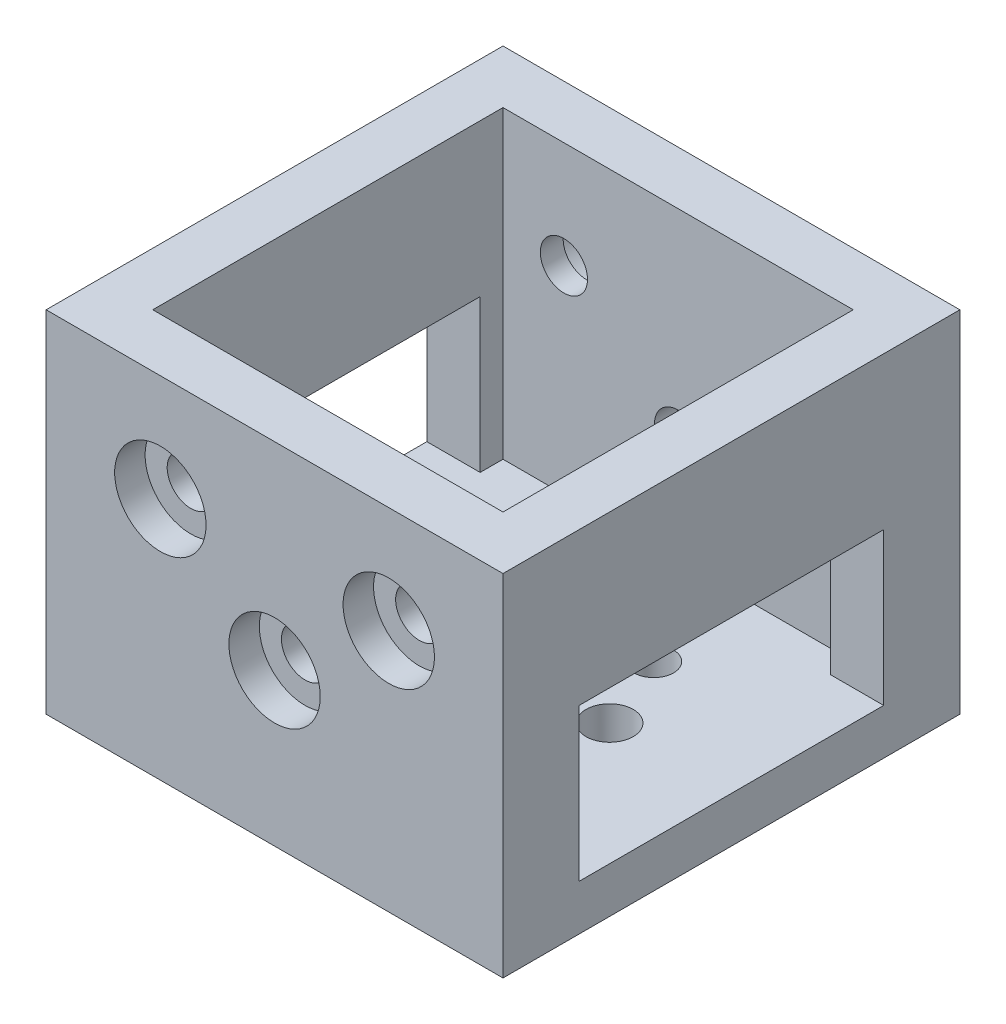
SolidWorks part; units mm, degrees
ref_plane "前视基准面" through (0, 0, 0) normal (0, 0, 1) x (1, 0, 0)
ref_plane "上视基准面" through (0, 0, 0) normal (0, 1, 0) x (1, 0, 0)
ref_plane "右视基准面" through (0, 0, 0) normal (1, 0, 0) x (0, 0, -1)
sketch "草图1" plane through (0, 0, 0) normal (0, 1, 0) x (1, 0, 0)
  line L0 (0, 0) -> (0, 11.5) construction
  line L1 (0, 0) -> (0, -11.5) construction
  line L2 (0, 0) -> (11.5, 0) construction
  line L3 (0, 0) -> (-11.5, 0) construction
  line L4 (0, 11.5) -> (11.5, 11.5)
  line L5 (11.5, 11.5) -> (11.5, 0)
  line L6 (11.5, -11.5) -> (0, -11.5)
  line L7 (-11.5, -11.5) -> (-11.5, 0)
  line L8 (-11.5, 11.5) -> (0, 11.5)
  line L9 (-11.5, 0) -> (-11.5, 11.5)
  line L10 (-11.5, -11.5) -> (0, -11.5)
  line L11 (11.5, -11.5) -> (11.5, 0)
  line L12 (-11.5, -11.5) -> (-11.5, -15)
  line L13 (11.5, -11.5) -> (11.5, -15)
  line L14 (-11.5, 15) -> (-11.5, 11.5)
  line L15 (11.5, 11.5) -> (11.5, 15)
  line L19 (-11.5, 15) -> (11.5, 15)
  line L22 (11.5, -15) -> (-11.5, -15)
  line L28 (-11.5, -11.5) -> (-8.5, -11.5)
  line L30 (11.5, 15) -> (15, 15)
  line L32 (15, 15) -> (15, -15)
  line L33 (11.5, -15) -> (15, -15)
  line L34 (-11.5, -15) -> (-15, -15)
  line L35 (-15, -15) -> (-15, 15)
  line L36 (-15, 15) -> (-11.5, 15)
extrude "凸台-拉伸2" add sketch "草图1" along normal blind 3 contours L6 L11 L5 L4 L8 L9 L7 L10 | L8 L4 | L6 L10 region at (0, 0, -13.25) region at (0, 0, 0) region at (0, 0, 13.25)
extrude "凸台-拉伸3" add sketch "草图1<4>" along normal blind 18 separate body contours L22 | L19 region at (0, 0, -13.25) region at (0, 0, 13.25)
sketch "草图1<4>" plane through (0, 0, 0) normal (0, 1, 0) x (1, 0, 0) same geometry as "草图1"
extrude "凸台-拉伸4" add sketch "草图1<5>" along normal blind 23 contours L36 L35 L34 L7 L9 | L33 L32 L30 L5 L11 | L10 | L6 | L4 | L8 region at (0, 0, -13.25) region at (13.25, 0, 0) region at (-13.25, 0, 0) region at (0, 0, 13.25)
sketch "草图1<5>" plane through (0, 0, 0) normal (0, 1, 0) x (1, 0, 0) same geometry as "草图1"
sketch "草图3" plane through (0, 0, -19.6) normal (0, 0, -1) x (-1, 0, 0)
  line L0 (15, 13) -> (15, 16)
  line L1 (-15, 23) -> (-15, 0) construction
  line L2 (-15, 8) -> (-15, 13)
  line L3 (15, 16) -> (7.5, 16) construction
  line L4 (15, 23) -> (15, 0) construction
  line L5 (15, 8) -> (15, 13)
  line L6 (0, 0) -> (0, 10) construction
  line L7 (-15, 8) -> (-7.5, 8) construction
  line L8 (15, 8) -> (7.5, 8) construction
  line L9 (17.5, 0) -> (-17.5, 0) construction
  line L10 (7.5, 16) -> (-7.5, 16) construction
  circle A0 centre (0, 10) radius 1.55
  circle A1 centre (-7.5, 16) radius 1.55
  circle A2 centre (7.5, 16) radius 1.55
extrude "切除-拉伸2" cut sketch "草图3" against normal through all contours A2 | A0 | A1 region at (0, 10, -19.6) region at (7.5, 16, -19.6) region at (-7.5, 16, -19.6)
sketch "草图8" plane through (-15, 0, 0) normal (-1, 0, 0) x (0, 0, 1)
  line L0 (10, 10) -> (10, 3)
  line L1 (0, 3) -> (10, 3)
  line L2 (10, 10) -> (10, 13)
  line L3 (-10, 3) -> (0, 3)
  line L10 (-10, 3) -> (-10, 13)
  line L11 (-10, 13) -> (10, 13)
extrude "切除-拉伸5" cut sketch "草图8" against normal through all contours L11 L10 L2 region at (-15, 8, 0)
sketch "草图9" plane through (0, 0, 0) normal (0, -1, 0) x (1, 0, 0)
  line L0 (0, 0) -> (-7, 0) construction
  line L1 (0, 0) -> (7, 0) construction
  line L2 (0, 0) -> (0, -7) construction
  line L3 (0, 0) -> (0, 7) construction
  line L4 (0, 7) -> (-7, 7) construction
  line L5 (-7, 7) -> (-7, 0) construction
  line L6 (-7, 0) -> (-7, -7) construction
  line L7 (-7, -7) -> (0, -7) construction
  line L8 (7, -7) -> (7, 0) construction
  line L9 (7, -7) -> (0.5896, -7) construction
  line L10 (7, 0) -> (7, 7) construction
  line L11 (7, 7) -> (0, 7) construction
  line L12 (-7, 7) -> (7, -7) construction
  line L13 (-7, -7) -> (7, 7) construction
  line L14 (0, 0) -> (-4.9497, 4.9497) construction
  line L15 (0, 0) -> (-4.9497, -4.9497) construction
  line L16 (0, 0) -> (4.9497, -4.9497) construction
  line L17 (0, 0) -> (4.9497, 4.9497) construction
  circle A0 centre (-4.9497, -4.9497) radius 1.3
  circle A1 centre (4.9497, -4.9497) radius 1.3
  circle A2 centre (4.9497, 4.9497) radius 1.3
  circle A3 centre (-4.9497, 4.9497) radius 1.3
  circle A4 centre (0, 0) radius 3
  circle A5 centre (7, 0) radius 1.55
  circle A6 centre (0, 7) radius 1.55
  circle A7 centre (0, -7) radius 1.55
  circle A8 centre (-7, 0) radius 1.55
extrude "切除-拉伸6" cut sketch "草图9" against normal through all
sketch "草图10" plane through (0, 0, -15) normal (0, 0, -1) x (-1, 0, 0)
  circle A0 centre (7.5, 16) radius 3
  circle A1 centre (0, 10) radius 3
  circle A2 centre (-7.5, 16) radius 3
extrude "切除-拉伸7" cut sketch "草图10" against normal blind 2
sketch "草图11" plane through (0, 0, 15) normal (0, 0, 1) x (1, 0, 0)
  circle A0 centre (-7.5, 16) radius 3
  circle A1 centre (0, 10) radius 3
  circle A2 centre (7.5, 16) radius 3
extrude "切除-拉伸8" cut sketch "草图11" against normal blind 2
